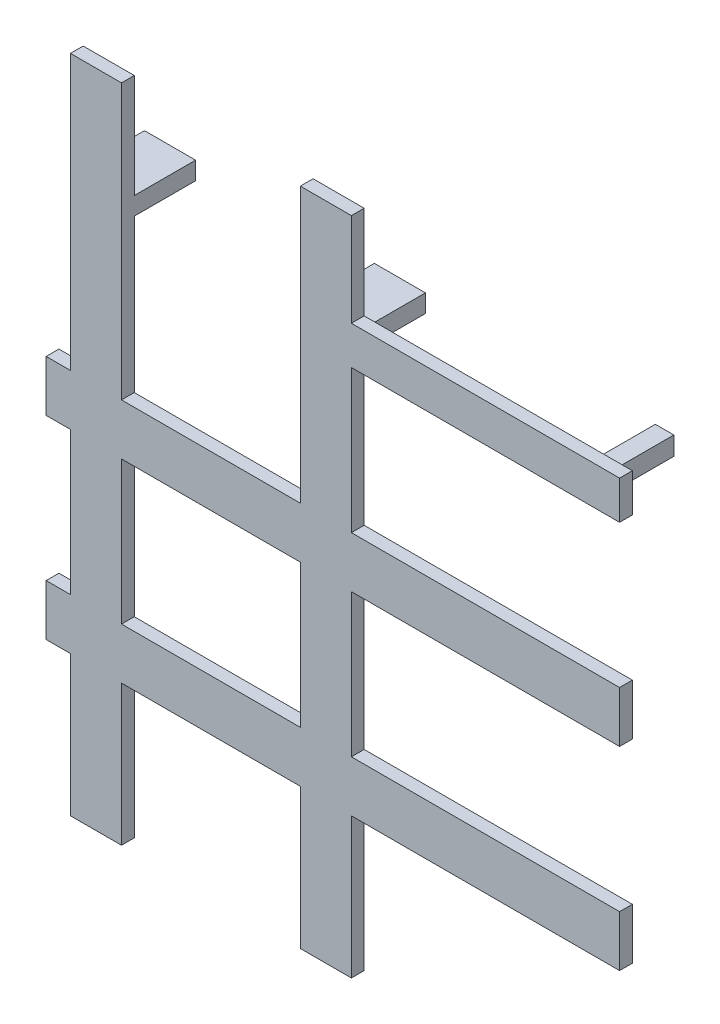
SolidWorks part; units mm, degrees
ref_plane "Piano frontale" through (0, 0, 0) normal (0, 0, 1) x (1, 0, 0)
ref_plane "Piano superiore" through (0, 0, 0) normal (0, 1, 0) x (1, 0, 0)
ref_plane "Piano destro" through (0, 0, 0) normal (1, 0, 0) x (0, 0, -1)
sketch "Schizzo1" plane through (0, 0, 0) normal (0, 0, 1) x (1, 0, 0)
  line L1 (0, 0) -> (4, 0)
  line L2 (0, 0) -> (0, 51.7)
  line L3 (0, 51.7) -> (4, 51.7)
  line L4 (4, 0) -> (4, 51.7)
  dimension "D1" = 4
  dimension "D2" = 51.7
extrude "Estrusione-Estrusione1" add sketch "Schizzo1" along normal blind 1
sketch "Schizzo2" plane through (4, 0, 0) normal (1, 0, 0) x (0, 0, -1)
  line L1 (-1, 0) -> (-1, 51.7) construction
  line L2 (0, 0) -> (0, 51.7) construction
  line L3 (-1, 30.2) -> (0, 30.2)
  line L4 (-1, 30.2) -> (-1, 26.2)
  line L5 (-1, 26.2) -> (0, 26.2)
  line L6 (0, 30.2) -> (0, 26.2)
  dimension "D2" = 4
extrude "Estrusione-Estrusione2" add sketch "Schizzo2" along normal blind 18 and the other way blind 5.9
sketch "Schizzo3" plane through (4, 0, 0) normal (1, 0, 0) x (0, 0, -1)
  line L1 (-1, 0) -> (-1, 26.2) construction
  line L2 (0, 0) -> (0, 26.2) construction
  line L3 (-1, 15) -> (0, 15)
  line L4 (-1, 15) -> (-1, 11)
  line L5 (-1, 11) -> (0, 11)
  line L6 (0, 15) -> (0, 11)
  dimension "D2" = 4
extrude "Estrusione-Estrusione3" add sketch "Schizzo3" along normal blind 18 and the other way blind 5.9
sketch "Schizzo4" plane through (0, 30.2, 0) normal (0, 1, 0) x (1, 0, 0)
  line L0 (4, 0) -> (22, 0) construction
  line L1 (22, -1) -> (18, -1)
  line L2 (22, -1) -> (22, 0)
  line L3 (22, 0) -> (18, 0)
  line L4 (18, -1) -> (18, 0)
  dimension "D1" = 4
extrude "Estrusione-Estrusione4" add sketch "Schizzo4" along normal blind 21.5 and the other way blind 30.2
sketch "Schizzo5" plane through (22, 0, 0) normal (1, 0, 0) x (0, 0, -1)
  line L0 (0, 0) -> (0, 51.7) construction
  line L1 (0, 44.3987) -> (-1, 44.3987)
  line L2 (0, 44.3987) -> (0, 41.3987)
  line L3 (0, 41.3987) -> (-1, 41.3987)
  line L4 (-1, 44.3987) -> (-1, 41.3987)
  line L5 (-1, 51.7) -> (-1, 0) construction
  dimension "D1" = 3
extrude "Estrusione-Estrusione5" add sketch "Schizzo5" along normal blind 21
sketch "Schizzo7" plane through (22, 0, 0) normal (1, 0, 0) x (0, 0, -1)
  line L1 (-1, 41.3987) -> (-1, 0) construction
  line L2 (0, 0) -> (0, 41.3987) construction
  line L3 (-1, 11) -> (0, 11)
  line L4 (-1, 11) -> (-1, 15)
  line L5 (-1, 15) -> (0, 15)
  line L6 (0, 11) -> (0, 15)
  dimension "D2" = 4
extrude "Estrusione-Estrusione6" add sketch "Schizzo7" along normal blind 21
sketch "Schizzo8" plane through (22, 0, 0) normal (1, 0, 0) x (0, 0, -1)
  line L1 (-1, 41.3987) -> (-1, 15) construction
  line L2 (0, 15) -> (0, 41.3987) construction
  line L3 (-1, 26.2) -> (0, 26.2)
  line L4 (-1, 26.2) -> (-1, 30.2)
  line L5 (-1, 30.2) -> (0, 30.2)
  line L6 (0, 26.2) -> (0, 30.2)
  dimension "D2" = 4
extrude "Estrusione-Estrusione7" add sketch "Schizzo8" along normal blind 21
sketch "Schizzo10" plane through (0, 0, 0) normal (0, 0, -1) x (-1, 0, 0)
  line L1 (-4, 30.2) -> (-4, 51.7) construction
  line L2 (0, 51.7) -> (0, 30.2) construction
  line L3 (-4, 42.16) -> (0, 42.16)
  line L4 (-4, 42.16) -> (-4, 43.56)
  line L5 (-4, 43.56) -> (0, 43.56)
  line L6 (0, 42.16) -> (0, 43.56)
  dimension "D2" = 1.4
extrude "Estrusione-Estrusione9" add sketch "Schizzo10" along normal blind 4.8
sketch "Schizzo11" plane through (0, 0, 0) normal (0, 0, -1) x (-1, 0, 0)
  line L1 (-18, 30.2) -> (-18, 51.7) construction
  line L3 (-18, 42.16) -> (-22, 42.16)
  line L4 (-18, 42.16) -> (-18, 43.56)
  line L5 (-18, 43.56) -> (-22, 43.56)
  line L6 (-22, 42.16) -> (-22, 43.56)
  dimension "D2" = 4
  dimension "D3" = 1.4
extrude "Estrusione-Estrusione10" add sketch "Schizzo11" along normal blind 4.8
sketch "Schizzo12" plane through (0, 0, 0) normal (0, 0, -1) x (-1, 0, 0)
  line L4 (-41.45, 43.6487) -> (-40, 43.6487)
  line L5 (-41.45, 43.6487) -> (-41.45, 42.1987)
  line L6 (-41.45, 42.1987) -> (-40, 42.1987)
  line L7 (-40, 43.6487) -> (-40, 42.1987)
  dimension "D3" = 1.45
  dimension "D4" = 1.45
extrude "Estrusione-Estrusione11" add sketch "Schizzo12" along normal blind 4.8
